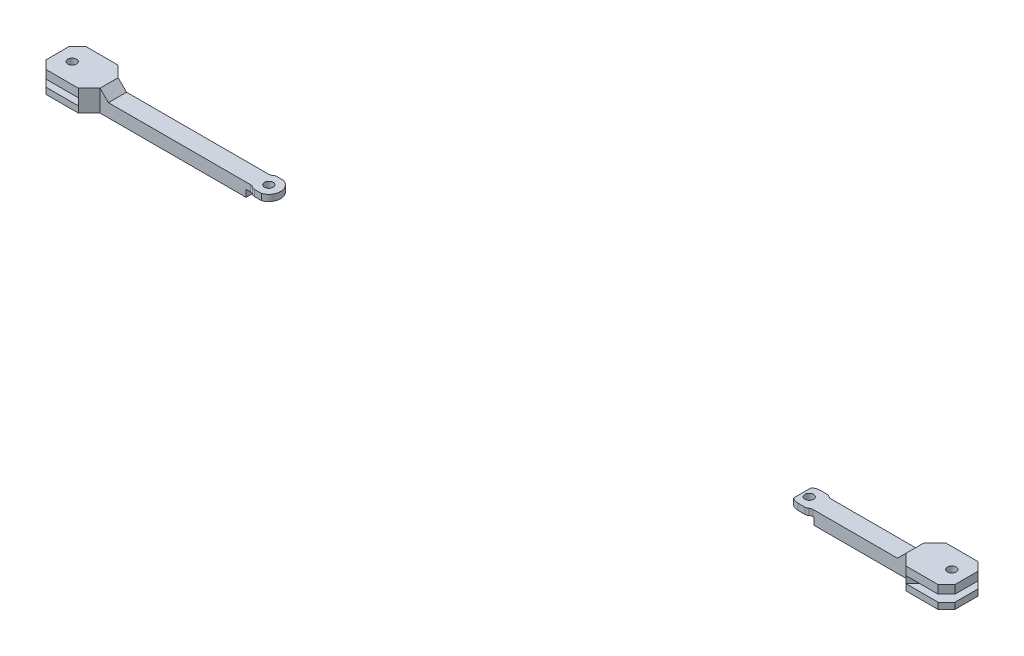
SolidWorks part; units mm, degrees
material "PA 类型 6"
ref_plane "前视基准面" through (0, 0, 0) normal (0, 0, 1) x (1, 0, 0)
ref_plane "上视基准面" through (0, 0, 0) normal (0, 1, 0) x (1, 0, 0)
ref_plane "右视基准面" through (0, 0, 0) normal (1, 0, 0) x (0, 0, -1)
sketch "参考" plane through (0, 0, 0) normal (0, 1, 0) x (1, 0, 0)
  line L0 (0, 0) -> (106.7, 0) construction
  line L1 (106.7, 0) -> (157.8766, 0) construction
  line L2 (104.25, 4.1) -> (104.25, -4.1) construction
  line L3 (105.15, 0) -> (105.15, 4.8906) construction
  line L4 (111.35, 8.7614) -> (111.35, -7.929) construction
  line L5 (0, 0) -> (0, 91.7169) construction
  line L6 (104.25, 4.1) -> (88.75, 4.1)
  line L7 (152.6266, 3.75) -> (153.8766, 2.5)
  line L8 (153.8766, 2.5) -> (153.8766, -2.5)
  line L9 (153.8766, -2.5) -> (152.6266, -3.75)
  line L10 (88.75, 4.1) -> (88.75, -4.1)
  line L11 (88.75, -4.1) -> (104.25, -4.1)
  line L12 (96.5, 4.1) -> (96.5, 18.0028) construction
  circle A0 centre (106.7, 0) radius 1.55
  circle A1 centre (157.8766, 0) radius 1.55
  circle A2 centre (-87.3, 0) radius 1.55
  circle A3 centre (86.3, 0) radius 1.55
  dimension "D3" = 3.1
  dimension "D12" = 3.1
  dimension "D1" = 51.1766
  dimension "D2" = 106.7
  dimension "D4" = 4
  dimension "D5" = 7.5
  dimension "D6" = 135
  dimension "D7" = 5
  dimension "D8" = 1.25
  dimension "D9" = 0.9
  dimension "D10" = 7.1
  dimension "D11" = 87.3
  dimension "D13" = 15.5
  dimension "D14" = 8.2
sketch "主结构-草图" plane through (0, 0, 0) normal (0, 1, 0) x (1, 0, 0)
  line L0 (0, 0) -> (103.2286, 75) construction
  line L1 (0, 0) -> (106.7, 0) construction
  line L2 (106.7, 0) -> (157.8766, 0) construction
  line L3 (111.35, 3.25) -> (144.6157, 3.25)
  line L4 (144.6157, 3.25) -> (148.5176, 7.1519)
  line L5 (106.7, 4) -> (109.1, 4)
  line L6 (152.6266, 3.75) -> (153.8766, 2.5) construction
  line L7 (148.5176, 7.1519) -> (153.3766, 2.2929)
  line L8 (153.3766, 2.2929) -> (153.3766, -2.2929)
  line L9 (153.8766, 2.5) -> (153.8766, -2.5) construction
  line L10 (0, 0) -> (293.1134, 0) construction
  line L11 (111.35, -3.25) -> (144.6157, -3.25)
  line L12 (148.5176, -7.1519) -> (153.3766, -2.2929)
  line L13 (144.6157, -3.25) -> (148.5176, -7.1519)
  line L14 (148.5176, 7.1519) -> (163.1266, 7.1519)
  line L15 (163.1266, 7.1519) -> (163.1266, -7.1519)
  line L16 (163.1266, -7.1519) -> (148.5176, -7.1519)
  line L17 (106.7, -4) -> (109.1, -4)
  line L18 (104.25, 3.1619) -> (104.25, -4.1)
  line L19 (104.25, 4.1) -> (104.25, -4.1) construction
  line L20 (111.35, 8.7614) -> (111.35, -7.929) construction
  line L21 (111.6, 3.25) -> (111.6, -3.25)
  line L22 (144.6157, 3.25) -> (144.6157, -3.25)
  circle A0 centre (106.7, 0) radius 1.55
  circle A1 centre (103.2286, 75) radius 70.25 construction
  circle A2 centre (157.8766, 0) radius 1.55
  arc A4 (106.7, 4) -> (106.7, -4) centre (106.7, 0) ccw
  arc A5 (111.35, 3.25) -> (110.1807, 3.6398) centre (111.35, 5.1989) cw
  arc A6 (110.1807, 3.6398) -> (109.1, 4) centre (109.1, 2.1989) ccw
  arc A7 (111.35, -3.25) -> (110.1807, -3.6398) centre (111.35, -5.1989) ccw
  arc A8 (110.1807, -3.6398) -> (109.1, -4) centre (109.1, -2.1989) cw
  point P29 (153.3766, 0)
  dimension "D3" = 140.5
  dimension "D4" = 3.1
  dimension "D1" = 36
  dimension "D2" = 75
  dimension "D5" = 0.5
  dimension "D6" = 0.5
  dimension "D7" = 80
  dimension "D8" = 3.25
  dimension "D9" = 5.25
  dimension "D10" = 8
  dimension "D11" = 2.25
  dimension "D12" = 0.25
extrude "下部底座" add sketch "主结构-草图" against normal blind 2.25 contours L3 L11 L13 L12 L8 L7 L4 A0 | L16 L15 L14 L7 L8 L12 A2 | L22 L3 L21 L11 region at (128.1079, 0, 0) region at (148.7847, 0, 0) region at (155.8221, 0, -6.9474)
extrude "配平" add sketch "主结构-草图<4>" along normal blind 0.25 from surface contours L3 L21 L11 L13 L12 L8 L7 L4 | L22 L3 L21 L11 region at (128.1079, 0, 0) region at (148.7847, 0, 0) starting at face at (141.965, 0, 0)
sketch "主结构-草图<4>" plane through (0, 0, 0) normal (0, 1, 0) x (1, 0, 0) same geometry as "主结构-草图"
extrude "中部支撑" add sketch "主结构-草图<3>" along normal blind 2.25 from surface contours A8 A7 L11 L21 L3 A5 A6 L5 A4 L18 L17 A0 | L3 L21 L11 L13 L12 L8 L7 L4 | L22 L3 L21 L11 region at (111.475, 0, -3.1414) region at (128.1079, 0, 0) region at (148.7847, 0, 0) starting at face at (139.5275, 0.25, 0)
sketch "主结构-草图<3>" plane through (0, 0, 0) normal (0, 1, 0) x (1, 0, 0) same geometry as "主结构-草图"
extrude "凸台-拉伸4" add sketch "主结构-草图<5>" along normal blind 3 from surface contours L4 L22 L13 L12 L8 L7 | L16 L15 L14 L7 L8 L12 A2 region at (148.7847, 0, 0) region at (155.8221, 0, -6.9474) starting at face at (106.7, 2.5, -1.55)
sketch "主结构-草图<5>" plane through (0, 0, 0) normal (0, 1, 0) x (1, 0, 0) same geometry as "主结构-草图"
chamfer "倒角1" distance 3 1 edges at (144.6157, 2.5, 0)
chamfer "倒角2" distance 3 angle 45 4 edges at (163.1266, -1.125, -7.1519) (163.1266, -1.125, 7.1519) (163.1266, 4, 7.1519) (163.1266, 4, -7.1519)
mirror "镜向1" about plane through (0, 0, 0) normal (1, 0, 0) of bodies 110
sketch "草图6" plane through (0, 0, 0) normal (0, 1, 0) x (1, 0, 0)
  line L5 (-111.35, 3.25) -> (-102.3602, 3.25)
  line L6 (-102.3602, 3.25) -> (-102.3602, 7.4237)
  line L7 (-102.3602, 7.4237) -> (-111.35, 7.4237)
  line L8 (-111.35, 7.4237) -> (-111.35, 3.25)
  line L9 (0, 0) -> (-58.7628, 0) construction
  line L10 (-111.35, -7.4237) -> (-111.35, -3.25)
  line L11 (-102.3602, -7.4237) -> (-111.35, -7.4237)
  line L12 (-102.3602, -3.25) -> (-102.3602, -7.4237)
  line L13 (-111.35, -3.25) -> (-102.3602, -3.25)
extrude "多余切除" cut sketch "草图6" along normal through all
sketch "草图4" plane through (0, 0, 0) normal (0, 1, 0) x (1, 0, 0)
  line L0 (-90.65, 3.25) -> (-90.65, -3.25)
  line L1 (-83.3, 3.1457) -> (-86.3888, -4.118) construction
  line L2 (-85.9813, -4.0062) -> (-88.3813, -4.0062)
  line L3 (-85.9813, 4.0062) -> (-88.15, 4.0062)
  line L4 (0, 0) -> (0, -43.8915) construction
  line L5 (-90.65, 3.25) -> (-111.35, 3.25)
  line L6 (-111.35, 3.25) -> (-111.35, -3.25)
  line L7 (-111.35, -3.25) -> (-90.65, -3.25)
  line L8 (-104.3682, 3.25) -> (-141.6157, 3.25) construction
  line L9 (-104.3682, -3.25) -> (-141.6157, -3.25) construction
  line L10 (0, 0) -> (-30.2009, 0) construction
  arc A1 (-89.4625, -3.6536) -> (-88.3813, -4.0062) centre (-88.392, -2.2051) ccw
  arc A2 (-90.65, -3.25) -> (-89.4625, -3.6536) centre (-90.65, -5.1989) cw
  arc A3 (-89.4625, 3.6536) -> (-88.15, 4.0062) centre (-88.3735, 2.2189) cw
  arc A4 (-90.65, 3.25) -> (-89.4625, 3.6536) centre (-90.65, 5.1989) ccw
  arc A5 (-85.9813, 4.0062) -> (-85.9813, -4.0062) centre (-87.3, 0) cw
  circle A7 centre (-87.3, 0) radius 1.55 construction
  circle A12 centre (-87.3, 0) radius 1.55
  dimension "D1" = 3.1
  dimension "D2" = 2.45
  dimension "D3" = 2.5
extrude "对称侧螺丝位" add sketch "草图4" along normal up to surface (2.5 mm away) from surface contours L6 L7 L0 L5 | A5 L3 A3 A4 L0 A2 A1 L2 A12 region at (-89.9874, 0, -3.2492) region at (-101, 0, 0) up to face at (-106.7, 2.5, -1.55) starting at face at (-106.7, 0.25, -1.55)
sketch "草图7" plane through (0, 0, 0) normal (0, 1, 0) x (1, 0, 0)
  line L0 (-111.6, 3.25) -> (-92.2, 3.25)
  line L1 (-90.65, 3.25) -> (-111.6, 3.25) construction
  line L2 (-92.2, 3.25) -> (-92.2, -3.25)
  line L3 (-90.65, -3.25) -> (-111.6, -3.25) construction
  line L4 (-92.2, -3.25) -> (-111.6, -3.25)
  line L5 (-111.6, -3.25) -> (-111.6, 3.25)
  line L6 (-91.95, 3.25) -> (-91.95, -3.25) construction
  circle A0 centre (-87.3, 0) radius 1.55 construction
  dimension "D1" = 4.65
  dimension "D2" = 0.25
extrude "对称侧底部配合" add sketch "草图7" along normal up to next and the other way up to surface other way up to face at (-145.5973, -2.25, 0)
